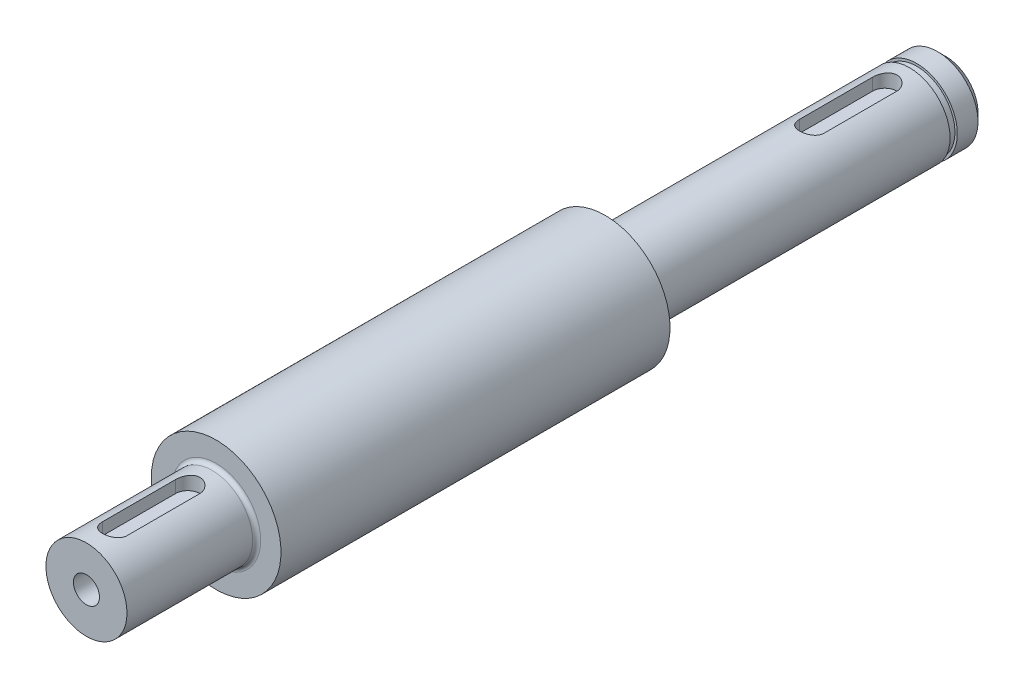
SolidWorks part; units mm, degrees
material "Cast Carbon Steel"
ref_plane "Front Plane" through (0, 0, 0) normal (0, 0, 1) x (1, 0, 0)
ref_plane "Top Plane" through (0, 0, 0) normal (0, 1, 0) x (1, 0, 0)
ref_plane "Right Plane" through (0, 0, 0) normal (1, 0, 0) x (0, 0, -1)
sketch "Sketch1" plane through (0, 0, 0) normal (0, 0, 1) x (1, 0, 0)
  circle A0 centre (0, 0) radius 12.7
  dimension "D1" = 25.4
extrude "Boss-Extrude1" add sketch "Sketch1" along normal mid plane 76.2
sketch "Sketch3" plane through (0, 0, -38.1) normal (0, 0, -1) x (-1, 0, 0)
  circle A0 centre (0, 0) radius 7.9375
  dimension "D1" = 15.875
extrude "Boss-Extrude2" add sketch "Sketch3" along normal blind 66.675
sketch "Sketch4" plane through (0, 0, 38.1) normal (0, 0, 1) x (1, 0, 0)
  circle A0 centre (0, 0) radius 7.9375
  dimension "D1" = 15.875
ref_plane "Plane1" through (0, 0, -98.425) normal (0, 0, -1) x (-1, 0, 0)
sketch "Sketch8" plane through (0, 0, -98.425) normal (0, 0, -1) x (-1, 0, 0)
  circle A0 centre (0, 0) radius 7.4676
  circle A1 centre (0, 0) radius 12.7
  dimension "D1" = 14.9352
  dimension "D2" = 25.4
extrude "Cut-Extrude1" cut sketch "Sketch8" against normal mid plane 1.4224
sketch "Sketch9" plane through (0, 0, 38.1) normal (0, 0, 1) x (1, 0, 0)
  circle A0 centre (0, 0) radius 7.9375
  dimension "D1" = 15.875
extrude "Boss-Extrude3" add sketch "Sketch9" along normal blind 25.4
fillet "Fillet1" radius 0.7937 2 edges at (7.9375, 0, 38.1) (7.9375, 0, -38.1)
hole_wizard "1/4-20 Tapped Hole1" positions "Sketch10" profile "Sketch12" tap size "1/4-20" standard "ANSI Inch"
sketch "Sketch10" plane through (0, 0, 63.5) normal (0, 0, 1) x (1, 0, 0)
  point P0 (0, 0)
sketch "Sketch12" plane through (0, 0, 63.5) normal (1, 0, 0) x (0, -1, 0)
  line L0 (0, 0) -> (0, 39.6338)
  line L1 (0, 39.6338) -> (2.5527, 38.1)
  line L2 (2.5527, 38.1) -> (2.5527, 0)
  line L5 (2.5527, 0) -> (0, 0)
  line L10 (0, 39.6338) -> (-2.5527, 38.1) construction
  line L11 (0, -6.35) -> (0, 107.95) construction
  dimension "Tap Drill Dia." = 5.1054
  dimension "Tap Drill Depth" = 38.1
  dimension "Drill Angle" = 118
cosmetic thread "Hole Thread1" parameters "D1"=31.75, "D2"=6.35
ref_plane "Plane2" through (0, 7.9375, 0) normal (0, 1, 0) x (1, 0, 0)
hole_wizard "3/16 (0.1875) Diameter Slot1" positions "Sketch13" profile "Sketch14" size "3/16" standard "ANSI Inch" slot yes
sketch "Sketch13" plane through (0, 7.9375, 0) normal (0, 1, 0) x (1, 0, 0)
  line L0 (0, 76.2) -> (0, 95.25) construction
  line L1 (0, -1000) -> (0, 49000) construction
  line L2 (7.9375, 104.775) -> (-7.9375, 104.775) construction
  line L3 (-7.9375, -63.5) -> (7.9375, -63.5) construction
  point P0 (0, 85.725)
  point P13 (0, -50.8)
  dimension "D1" = 19.05
  dimension "D2" = 12.7
sketch "Sketch14" plane through (0, 7.9375, -85.725) normal (1, 0, 0) x (0, 0, 1)
  line L0 (0, 0) -> (0, 2.747)
  line L1 (0, 2.747) -> (2.3812, 2.747)
  line L2 (2.3812, 2.747) -> (2.3812, 0)
  line L5 (2.3812, 0) -> (0, 0)
  line L10 (0, 2.747) -> (-2.3813, 2.747) construction
  line L11 (0, -6.35) -> (0, 107.95) construction
  dimension "Hole Dia." = 4.7625
  dimension "Hole Depth" = 2.747
  dimension "Drill Angle" = 180
chamfer "Chamfer1" distance 1.5875 angle 45 1 edges at (-7.9375, 0, -104.775)
